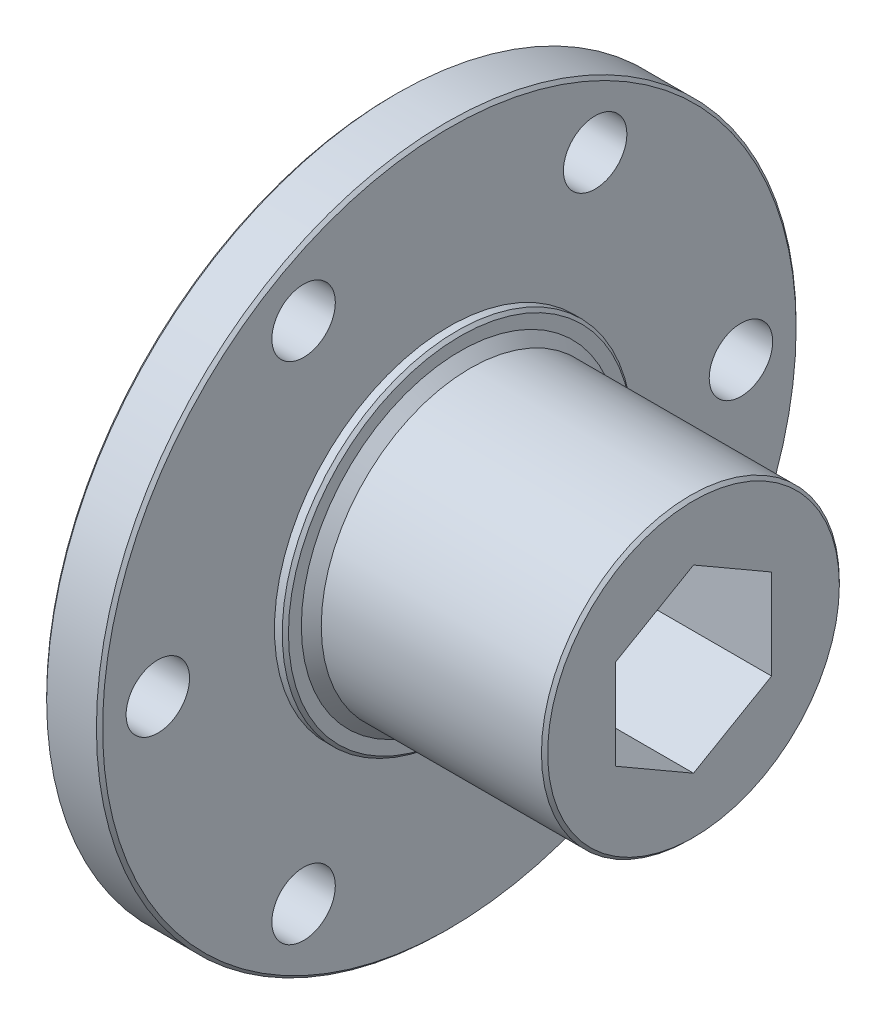
SolidWorks part; units mm, degrees
ref_plane "Front" through (0, 0, 0) normal (0, 0, 1) x (1, 0, 0)
ref_plane "Top" through (0, 0, 0) normal (0, 1, 0) x (1, 0, 0)
ref_plane "Right" through (0, 0, 0) normal (1, 0, 0) x (0, 0, -1)
ref_plane "Plane1" through (0, 0, 0) normal (0, 0, -1) x (-1, 0, 0)
sketch "Sketch1" plane through (0, 0, 0) normal (0, 0, -1) x (-1, 0, 0)
  line L0 (13.9241, 28.575) -> (13.9241, 0)
  line L1 (13.9241, 0) -> (18.4961, 0)
  line L2 (18.4961, 0) -> (18.4961, 28.575)
  line L3 (18.4961, 28.575) -> (13.9241, 28.575)
  line L4 (13.9241, 0) -> (18.4961, 0) construction
revolve "Revolve1" add sketch "Sketch1" angle 360 about L4 reverse direction yes
sketch "Sketch2" plane through (-18.4961, 0, 0) normal (-1, 0, 0) x (0, 0, 1)
  circle A0 centre (0, 0) radius 14.2875
extrude "Boss-Extrude1" add sketch "Sketch2" along normal blind 0.889
sketch "Sketch3" plane through (-13.9241, 0, 0) normal (1, 0, 0) x (0, 0, -1)
  circle A0 centre (0, 0) radius 14.2875
extrude "Boss-Extrude2" add sketch "Sketch3" along normal blind 0.889
sketch "Sketch4" plane through (-13.0351, 0, 0) normal (1, 0, 0) x (0, 0, -1)
  circle A0 centre (0, 0) radius 12.9794
extrude "Boss-Extrude3" add sketch "Sketch4" along normal blind 0.8128 draft 45
sketch "Sketch5" plane through (-12.2223, 0, 0) normal (1, 0, 0) x (0, 0, -1)
  circle A0 centre (0, 0) radius 12.1666
extrude "Boss-Extrude4" add sketch "Sketch5" along normal blind 18.2372
sketch "Sketch6" plane through (6.0149, 0, 0) normal (1, 0, 0) x (0, 0, -1)
  line L0 (0, -7.3617) -> (6.3754, -3.6809)
  line L1 (6.3754, -3.6809) -> (6.3754, 3.6808)
  line L2 (6.3754, 3.6808) -> (0, 7.3617)
  line L3 (0, 7.3617) -> (-6.3754, 3.6808)
  line L4 (-6.3754, 3.6808) -> (-6.3754, -3.6809)
  line L5 (-6.3754, -3.6809) -> (0, -7.3617)
extrude "Cut-Extrude1" cut sketch "Sketch6" against normal through all
hole_wizard "#6 (0.204) Diameter Hole1" positions "Sketch8" profile "Sketch7" hole size "#6" standard "ANSI Inch"
sketch "Sketch8" plane through (-18.4961, 0, 0) normal (-1, 0, 0) x (0, 0, 1)
  point P0 (11.9062, -20.6222)
  point P1 (-11.9062, -20.6222)
  point P2 (-23.8125, 0)
  point P3 (-11.9062, 20.6222)
  point P4 (11.9062, 20.6222)
  point P5 (23.8125, 0)
sketch "Sketch7" plane through (-18.4961, -20.6222, 11.9062) normal (0, 1, 0) x (0, 0, 1)
  line L0 (0, 0) -> (0, 24.511)
  line L1 (0, 24.511) -> (2.5908, 24.511)
  line L2 (2.5908, 24.511) -> (2.5908, 0)
  line L5 (2.5908, 0) -> (0, 0)
  line L11 (0, -6.35) -> (0, 107.95) construction
  dimension "Thru Hole Dia." = 5.1816
  dimension "Thru Hole Depth" = 24.511
chamfer "Chamfer1" distance 0.254 angle 45 5 edges at (-13.0351, 0, -14.2875) (6.0149, 0, -12.1666) (-19.3851, 0, 14.2875) (-13.9241, 0, 28.575) (-18.4961, 0, 28.575)
ref_axis "Hub Middle" through (0, 0, 0) along (1, 0, 0)
